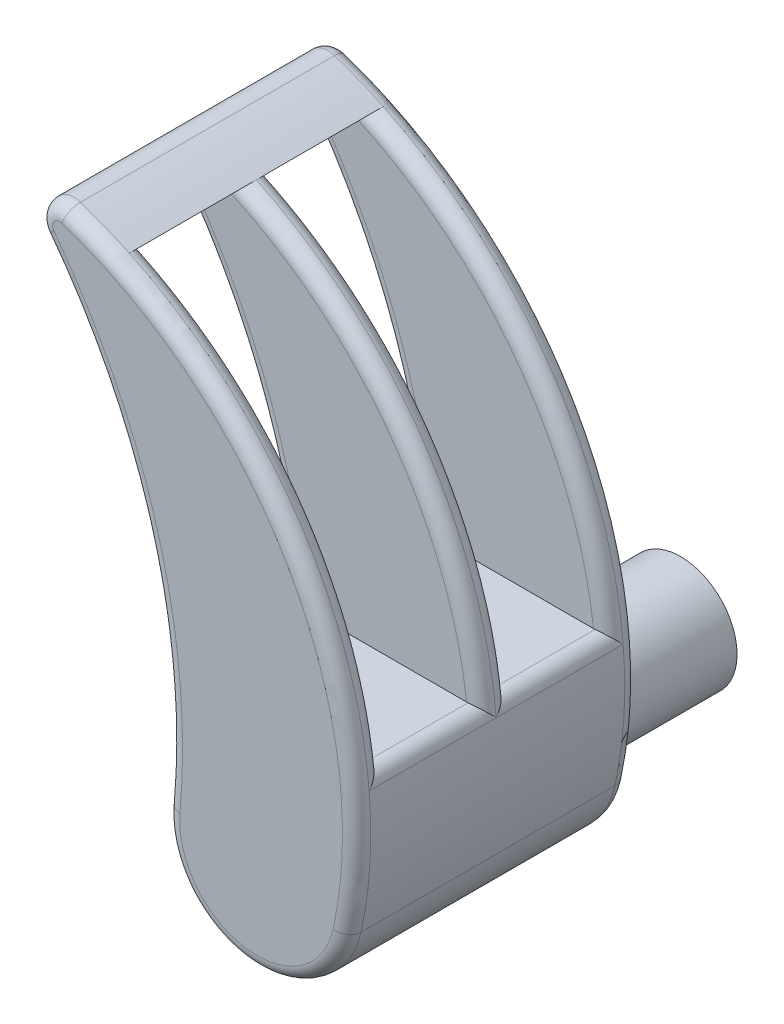
SolidWorks part; units mm, degrees
material "Aluminum 6061-T6"
ref_plane "Front Plane" through (0, 0, 0) normal (0, 0, 1) x (1, 0, 0)
ref_plane "Top Plane" through (0, 0, 0) normal (0, 1, 0) x (1, 0, 0)
ref_plane "Right Plane" through (0, 0, 0) normal (1, 0, 0) x (0, 0, -1)
sketch "Sketch1" plane through (0, 0, 0) normal (0, 0, 1) x (1, 0, 0)
  circle A0 centre (0, 0) radius 2
  dimension "D1" = 4
extrude "Boss-Extrude1" add sketch "Sketch1" along normal blind 5
sketch "Sketch2" plane through (0, 0, 5) normal (0, 0, 1) x (1, 0, 0)
  circle A0 centre (0, 0) radius 3.25
  dimension "D1" = 6.5
sketch "Sketch3" plane through (0, 0, 5) normal (0, 0, 1) x (1, 0, 0)
  line L0 (-3.25, 0) -> (3.25, 0) construction
  line L1 (0, 22.4857) -> (0, -6.7193) construction
  arc A5 (3.1756, -0.6915) -> (-3.237, 0.2902) centre (0, 0) cw
  arc A6 (-7.5992, 15.576) -> (-3.237, 0.2902) centre (-25.2775, 2.2658) cw
  arc A7 (-7.5992, 15.576) -> (-6.7642, 16.7391) centre (-7, 16.0271) cw
  arc A8 (-6.7642, 16.7391) -> (3.1756, -0.6915) centre (-11.481, 2.5) cw
extrude "Boss-Extrude3" add sketch "Sketch3" along normal blind 10
sketch "Sketch5" plane through (0, 0, 0) normal (1, 0, 0) x (0, 0, -1)
  line L0 (-15, 16.7391) -> (-15, -0.6915) construction
  line L10 (-14, 16.0437) -> (-10.5, 16.0437)
  line L12 (-14, 16.0437) -> (-14, 4.2437)
  line L13 (-14, 4.2437) -> (-10.5, 4.2437)
  line L14 (-10.5, 16.0437) -> (-10.5, 4.2437)
  line L15 (-9.5, 16.0437) -> (-6, 16.0437)
  line L16 (-9.5, 16.0437) -> (-9.5, 4.2437)
  line L17 (-9.5, 4.2437) -> (-6, 4.2437)
  line L18 (-6, 16.0437) -> (-6, 4.2437)
  line L19 (-5, -0.6915) -> (-5, 16.7391) construction
  dimension "D1" = 11.8
  dimension "D2" = 1
  dimension "D3" = 1
  dimension "D4" = 1
extrude "Cut-Extrude2" cut sketch "Sketch5" against normal up to surface and the other way up to surface up to face at (-4.7081, 8.1357, 10) other way up to face at (-0.1225, 8.9771, 10)
fillet "Fillet5" radius 0.5 24 edges at (-7.7139, 15.7972, 14) (-7.7139, 15.7972, 6) (-7.7139, 15.7972, 9.5) (-7.7139, 15.7972, 10.5) (-7.6092, 16.4645, 5) (1.5493, 9.9305, 5) (-0.4918, -3.2126, 5) (-0.4918, -3.2126, 15) (-3.9982, 8.3383, 15) (-7.6092, 16.4645, 15) (1.5493, 9.9305, 15) (-4.6257, 10.2149, 14) (-3.2372, 4.2437, 7.75) (-3.2372, 4.2437, 12.25) (0.7141, 11.2339, 14) (3.4173, 4.2437, 7.75) (3.4173, 4.2437, 12.25) (0.7141, 11.2339, 10.5) (0.7141, 11.2339, 9.5) (0.7141, 11.2339, 6) (-4.6257, 10.2149, 6) (-4.6257, 10.2149, 9.5) (-4.6257, 10.2149, 10.5) (-3.9982, 8.3383, 5)
